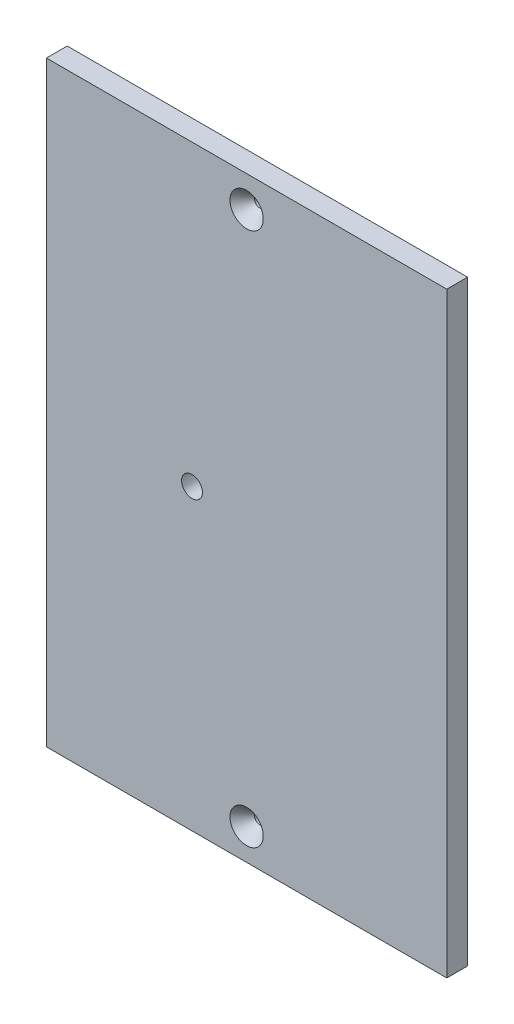
SolidWorks part; units mm, degrees
material "Beech"
ref_plane "Front Plane" through (0, 0, 0) normal (0, 0, 1) x (1, 0, 0)
ref_plane "Top Plane" through (0, 0, 0) normal (0, 1, 0) x (1, 0, 0)
ref_plane "Right Plane" through (0, 0, 0) normal (1, 0, 0) x (0, 0, -1)
sketch "Sketch1" plane through (0, 0, 0) normal (0, 0, 1) x (1, 0, 0)
  line L1 (-234.753, 19.05) -> (-356.9908, 19.05)
  line L2 (-234.753, 19.05) -> (-234.753, -163.1)
  line L3 (-234.753, -163.1) -> (-356.9908, -163.1)
  line L4 (-356.9908, 19.05) -> (-356.9908, -163.1)
  line L5 (-234.753, -163.1) -> (-350.6408, -163.1) construction
  line L6 (-350.6408, -144.05) -> (-350.6408, -163.1) construction
  dimension "D1" = 6.35
extrude "Boss-Extrude1" add sketch "Sketch1" along normal blind 6.35 contours L4 L3 L2 L1
hole_wizard "1/4 (0.25) Diameter Hole1" positions "Sketch4" profile "Sketch5" hole size "1/4" standard "ANSI Inch" end condition through all
sketch "Sketch4" plane through (0, 0, 6.35) normal (0, 0, 1) x (1, 0, 0)
  point P0 (-312.5408, -72.025)
sketch "Sketch5" plane through (-312.5408, -72.025, 6.35) normal (1, 0, 0) x (0, -1, 0)
  line L0 (0, 0) -> (0, 6.35)
  line L1 (0, 6.35) -> (3.175, 6.35)
  line L2 (3.175, 6.35) -> (3.175, 0)
  line L5 (3.175, 0) -> (0, 0)
  line L11 (0, -6.35) -> (0, 107.95) construction
  dimension "Thru Hole Dia." = 6.35
  dimension "Thru Hole Depth" = 6.35
hole_wizard "Hole1" positions "Sketch6" profile "Sketch7" legacy
sketch "Sketch6" plane through (181.0394, -72.025, 6.35) normal (0, 0, 1) x (0, 1, 0)
  line L0 (91.075, 476.9113) -> (-91.075, 476.9113) construction
  point P0 (81.55, 476.9113)
  point P2 (-81.55, 476.9113)
sketch "Sketch7" plane through (-295.8719, 9.525, 6.35) normal (1, 0, 0) x (0, -1, 0)
  line L0 (0, 0) -> (0, 32.7039)
  line L1 (0, 32.7039) -> (1.5875, 31.75)
  line L2 (1.5875, 31.75) -> (1.5875, 4.0177)
  line L3 (1.5875, 4.0177) -> (5.08, 0)
  line L4 (5.08, 0) -> (0, 0)
  line L5 (0, -14.3089) -> (0, 102.4216) construction
  line L6 (0, 32.7039) -> (-1.5875, 31.75) construction
  line L7 (-1.5875, 4.0177) -> (-5.08, 0) construction
  dimension "Diameter" = 3.175
  dimension "Depth" = 31.75
  dimension "C-Sink Diameter" = 10.16
  dimension "C-Sink Angle" = 82
  dimension "Drill Angle" = 118
